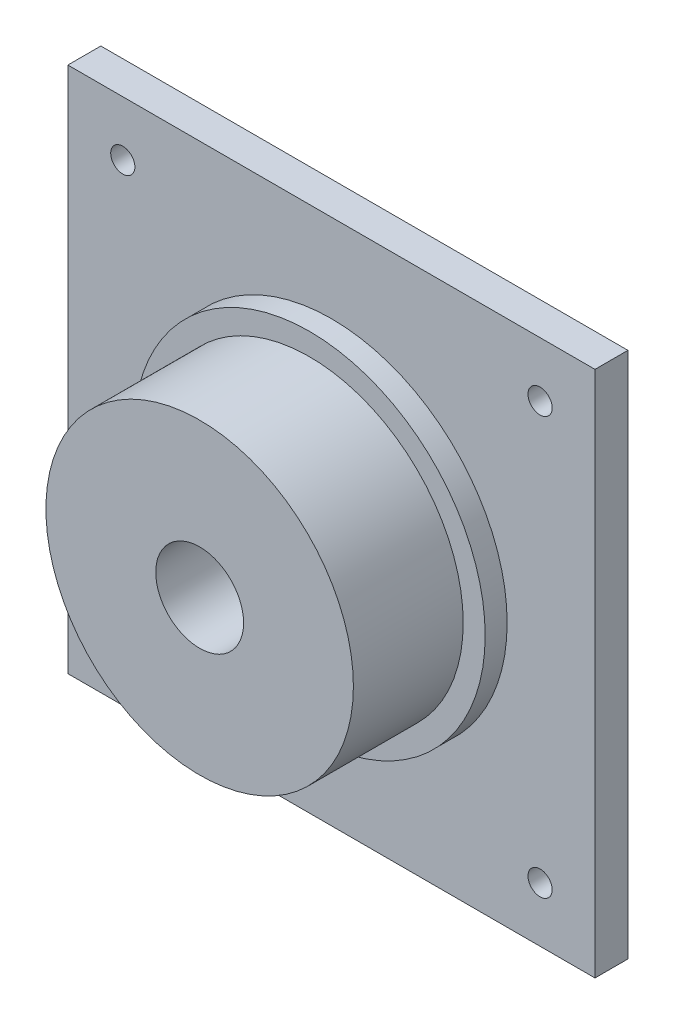
SolidWorks part; units mm, degrees
ref_plane "Front Plane" through (0, 0, 0) normal (0, 0, 1) x (1, 0, 0)
ref_plane "Top Plane" through (0, 0, 0) normal (0, 1, 0) x (1, 0, 0)
ref_plane "Right Plane" through (0, 0, 0) normal (1, 0, 0) x (0, 0, -1)
sketch "Sketch1" plane through (0, 0, 0) normal (0, 0, 1) x (1, 0, 0)
  line L1 (-120, -120) -> (120, -120)
  line L2 (-120, -120) -> (-120, 120)
  line L3 (-120, 120) -> (120, 120)
  line L4 (120, -120) -> (120, 120)
  line L5 (-120, -120) -> (120, 120) construction
  line L6 (-120, 120) -> (120, -120) construction
  circle A0 centre (0, 0) radius 20
  circle A1 centre (-95, -95) radius 5.5
  circle A2 centre (-95, 95) radius 5.5
  circle A3 centre (95, -95) radius 5.5
  circle A4 centre (95, 95) radius 5.5
  point P0 (0, 0)
extrude "Boss-Extrude1" add sketch "Sketch1" along normal blind 15
sketch "Sketch2" plane through (0, 0, 0) normal (0, 0, 1) x (1, 0, 0)
  circle A0 centre (0, 0) radius 70
  circle A1 centre (0, 0) radius 20
extrude "Boss-Extrude2" add sketch "Sketch2" along normal blind 75
sketch "Sketch3" plane through (0, 0, 0) normal (0, 0, 1) x (1, 0, 0)
  circle A0 centre (0, 0) radius 80
  circle A1 centre (0, 0) radius 40
  circle A2 centre (65, 0) radius 3
  circle A3 centre (45.9619, 45.9619) radius 3
  circle A4 centre (0, 65) radius 3
  circle A5 centre (-45.9619, 45.9619) radius 3
  circle A6 centre (-65, 0) radius 3
  circle A7 centre (-45.9619, -45.9619) radius 3
  circle A8 centre (0, -65) radius 3
  circle A9 centre (45.9619, -45.9619) radius 3
extrude "Boss-Extrude3" add sketch "Sketch3" along normal blind 25
ref_axis "Axis1" through (0, 0, -3.75) along (0, 0, 1)
sketch3d "3DSketch1"
  point P0 (0, 0, 0)
